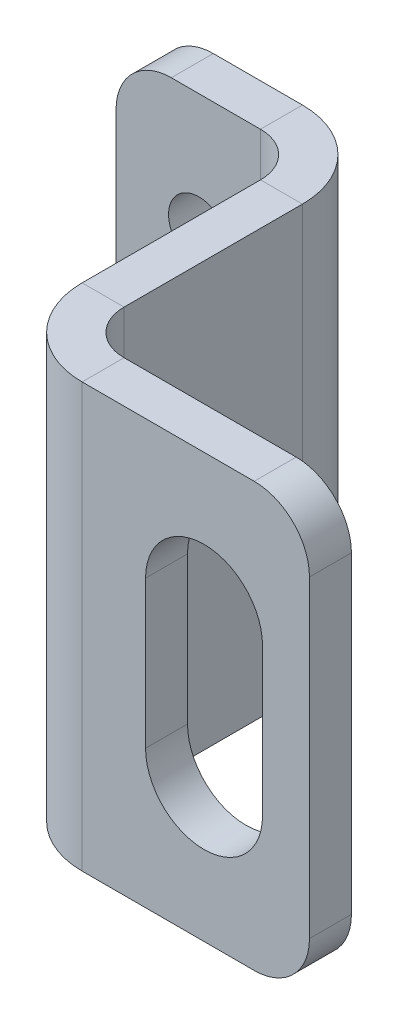
SolidWorks part; units mm, degrees
note: The reader was unsure of these and kept them because the rebuilt part matched: flange length of "Edge-Flange2", "Edge-Flange3".
material "Plain Carbon Steel"
ref_plane "Front Plane" through (0, 0, 0) normal (0, 0, 1) x (1, 0, 0)
ref_plane "Top Plane" through (0, 0, 0) normal (0, 1, 0) x (1, 0, 0)
ref_plane "Right Plane" through (0, 0, 0) normal (1, 0, 0) x (0, 0, -1)
sketch "Sketch1" plane through (0, 0, 0) normal (0, 0, 1) x (1, 0, 0)
  line L1 (-25, 23) -> (0, 23)
  line L2 (-25, 23) -> (-25, -23)
  line L3 (-25, -23) -> (0, -23)
  line L4 (0, 23) -> (0, -23)
  dimension "D1" = 25
  dimension "D2" = 46
sheet metal parameters "Sheet-Metal1" thickness 4.5542 parameters "D1"=4.7625
base flange "Base-Flange1" sketch "Sketch1" thickness 4.5542 reverse thickness direction no parameters "D1"=4.7625
edge flange "Edge-Flange2" sketch "Sketch9" flange angle 90 flange length 38 flange position material inside bend radius 4.7625 thickness 4.5542 parameters "D6"=10
sketch "Sketch9" plane through (0, 0, 0) normal (1, 0, 0) x (0, 1, 0)
  line L0 (-23, 0) -> (23, 0) construction
  line L1 (-23, 0) -> (23, 0)
  line L2 (-23, 0) -> (-23, 33.4458)
  line L3 (-23, 33.4458) -> (23, 33.4458)
  line L4 (23, 33.4458) -> (23, 0)
bend "EdgeBend2" bend radius 4.7625 bend angle 90 parameters "D5"=1
edge flange "Edge-Flange3" sketch "Sketch15" flange angle 90 flange length 34 flange position material inside bend radius 4.7625 thickness 4.5542 relief rectangular parameters "D6"=10
sketch "Sketch15" plane through (0, 0, 33.4458) normal (0, 0, 1) x (0, -1, 0)
  line L0 (-23, 0) -> (23, 0) construction
  line L1 (-23, 0) -> (23, 0)
  line L2 (-23, 0) -> (-23, 29.4458)
  line L3 (-23, 29.4458) -> (23, 29.4458)
  line L4 (23, 29.4458) -> (23, 0)
bend "EdgeBend3" bend radius 4.7625 bend angle 90 parameters "D5"=2
fillet "Fillet1" radius 6 4 edges at (-25, -23, -2.2771) (-25, 23, -2.2771) (29.4458, 23, 31.1687) (29.4458, -23, 31.1687)
hole_wizard "M6 Clearance Hole1" positions "Sketch11" profile "Sketch10" hole size "M6" standard "Peddi DIN" end condition through all
sketch "Sketch11" plane through (0, 0, 0) normal (0, 0, 1) x (1, 0, 0)
  line L0 (-16, -10) -> (-16, 10) construction
  line L2 (-16, 0) -> (0, 0) construction
  line L9 (0, -23) -> (0, 23) construction
  point P0 (-16, 10)
  point P2 (-16, -10)
  dimension "D1" = 16
  dimension "D4" = 20
sketch "Sketch10" plane through (-16, 10, 0) normal (1, 0, 0) x (0, -1, 0)
  line L0 (0, 0) -> (0, 4.5542)
  line L1 (0, 4.5542) -> (3.3, 4.5542)
  line L2 (3.3, 4.5542) -> (3.3, 0)
  line L5 (3.3, 0) -> (0, 0)
  line L11 (0, -6.35) -> (0, 107.95) construction
  dimension "Thru Hole Dia." = 6.6
  dimension "Thru Hole Depth" = 4.5542
sketch "Sketch12" plane through (-32.0142, 0, 33.4458) normal (0, 0, 1) x (1, 0, 0)
  line L0 (50.0142, -8) -> (50.0142, 8) construction
  line L1 (43.6642, -8) -> (43.6642, 8)
  line L2 (56.3642, -8) -> (56.3642, 8)
  line L4 (32.0142, 0) -> (50.0142, 0) construction
  arc A0 (43.6642, -8) -> (56.3642, -8) centre (50.0142, -8) ccw
  arc A1 (56.3642, 8) -> (43.6642, 8) centre (50.0142, 8) ccw
  circle A3 centre (16.0142, 10) radius 3.3 construction
  point P2 (50.0142, 0)
  dimension "D3" = 6.35
  dimension "D1" = 34
  dimension "D2" = 16
extrude "Cut-Extrude1" cut sketch "Sketch12" against normal through all normal cut yes
other "Freeze***"
flat pattern "Flat-Pattern1" [suppressed]
sketch "Bend-Lines1" plane through (0, 0, 0) normal (0, 0, 1) x (1, 0, 0)
  line L0 (23.4189, 12.7) -> (23.4189, -12.7) construction
  line L1 (23.4189, 12.7) -> (23.4189, -12.7) construction
sketch3d "Bounding-Box1" [suppressed]
  line L0 (0, 19.05, 0) -> (138.9127, 19.05, 0) construction
  line L1 (0, -19.05, 0) -> (138.9127, -19.05, 0) construction
  line L2 (0, 19.05, 0) -> (0, -19.05, 0) construction
  line L3 (138.9127, 19.05, 0) -> (138.9127, -19.05, 0) construction
bend of the flat pattern "Flatten-<EdgeBend2>1"
bend of the flat pattern "Flatten-<EdgeBend3>1"
